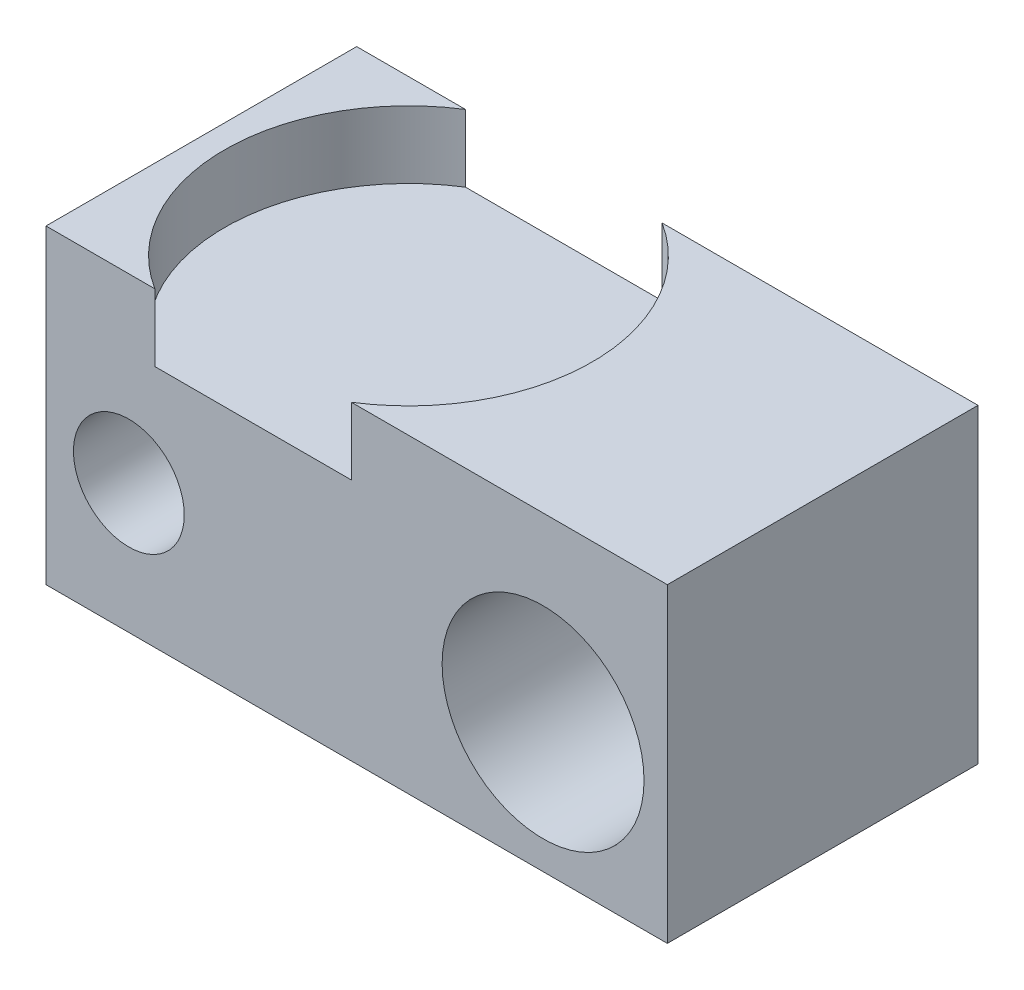
SolidWorks part; units mm, degrees
ref_plane "Front Plane" through (0, 0, 0) normal (0, 0, 1) x (1, 0, 0)
ref_plane "Top Plane" through (0, 0, 0) normal (0, 1, 0) x (1, 0, 0)
ref_plane "Right Plane" through (0, 0, 0) normal (1, 0, 0) x (0, 0, -1)
sketch "Sketch1" plane through (0, 0, 0) normal (0, 0, 1) x (1, 0, 0)
  line L1 (-30, -12.5) -> (30, -12.5)
  line L2 (-30, -12.5) -> (-30, 12.5)
  line L3 (-30, 12.5) -> (30, 12.5)
  line L4 (30, -12.5) -> (30, 12.5)
  line L5 (-30, -12.5) -> (30, 12.5) construction
  line L6 (-30, 12.5) -> (30, -12.5) construction
  circle A0 centre (18, 0) radius 9.75
  circle A1 centre (-22, 0) radius 5.35
  point P0 (0, 0)
  dimension "D2" = 10.7
  dimension "D3" = 19.5
  dimension "D5" = 8
  dimension "D7" = 12.5
  dimension "D1" = 40
  dimension "D4" = 12
  dimension "D6" = 25
  dimension "D8" = 0
extrude "Boss-Extrude1" add sketch "Sketch1" along normal blind 30
sketch "Sketch2" plane through (0, 12.5, 0) normal (0, 1, 0) x (1, 0, 0)
  line L0 (-30, -30) -> (-30, 0) construction
  circle A0 centre (-10, -15) radius 17.75
  line M1 (30, 0) -> (-30, 0)
  line M2 (-30, 0) -> (-30, -30)
  line M3 (-30, -30) -> (30, -30)
  line M4 (30, -30) -> (30, 0)
  dimension "D1" = 20
  dimension "36" = 35.5
extrude "Boss-Extrude2" add sketch "Sketch2" along normal blind 5 contours A0 M1 M2 M3 | A0 M3 M4 M1 region at (17.5486, 12.5, 15) region at (-28.0679, 12.5, 15)
extrude "Cut-Extrude1" cut sketch "Sketch2<3>" against normal blind 1.5
sketch "Sketch2<3>" plane through (0, 12.5, 0) normal (0, 1, 0) x (1, 0, 0) same geometry as "Sketch2"
